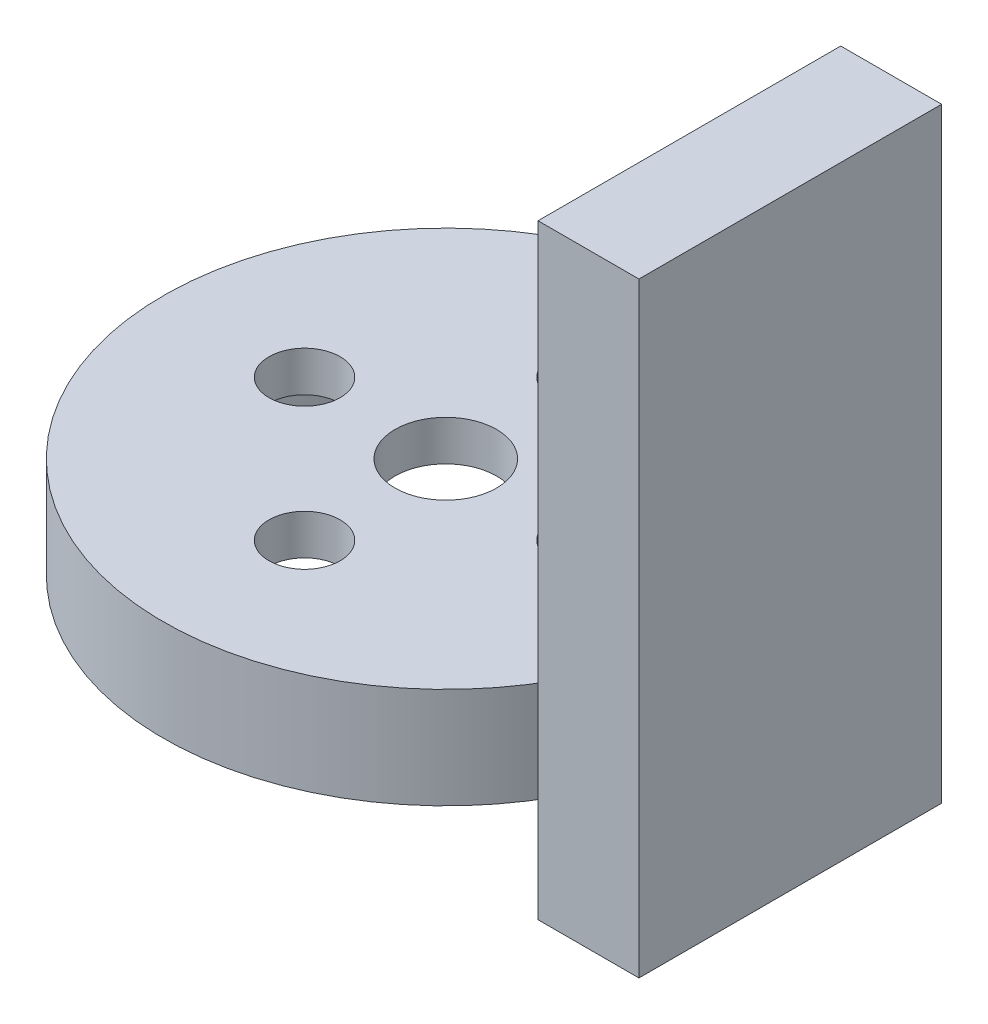
SolidWorks part; units mm, degrees
ref_plane "Front Plane" through (0, 0, 0) normal (0, 0, 1) x (1, 0, 0)
ref_plane "Top Plane" through (0, 0, 0) normal (0, 1, 0) x (1, 0, 0)
ref_plane "Right Plane" through (0, 0, 0) normal (1, 0, 0) x (0, 0, -1)
sketch "Sketch1" plane through (0, 0, 0) normal (0, 1, 0) x (1, 0, 0)
  circle A0 centre (0, 0) radius 14
  circle A1 centre (0, 0) radius 2.5173
  circle A2 centre (0, 7) radius 1.7621
  circle A3 centre (7, 0) radius 1.7621
  circle A4 centre (0, -7) radius 1.7621
  circle A5 centre (-7, 0) radius 1.7621
  point P15 (0, 0)
  dimension "D1" = 7
  dimension "D3" = 28
  dimension "D2" = 4
extrude "Boss-Extrude1" add sketch "Sketch1" along normal blind 5
sketch "Sketch4" plane through (0, 5, 0) normal (0, 1, 0) x (1, 0, 0)
  line L1 (22.0715, -2.5) -> (10.0715, -2.5)
  line L2 (22.0715, -2.5) -> (22.0715, 2.5)
  line L3 (22.0715, 2.5) -> (10.0715, 2.5)
  line L4 (10.0715, -2.5) -> (10.0715, 2.5)
  line L5 (22.0715, -2.5) -> (10.0715, 2.5) construction
  line L6 (22.0715, 2.5) -> (10.0715, -2.5) construction
  point P0 (16.0715, 0)
  dimension "D1" = 5
  dimension "D2" = 0
  dimension "D3" = 12
extrude "Boss-Extrude4" add sketch "Sketch4" against normal blind 5
sketch "Sketch6" plane through (0, 0, 0) normal (0, -1, 0) x (1, 0, 0)
  line L1 (22.0715, -2.5) -> (17.0715, -2.5)
  line L2 (22.0715, -2.5) -> (22.0715, 12.5)
  line L3 (22.0715, 12.5) -> (17.0715, 12.5)
  line L4 (17.0715, -2.5) -> (17.0715, 12.5)
  dimension "D1" = 5
  dimension "D2" = 15
extrude "Boss-Extrude5" add sketch "Sketch6" against normal blind 30
sketch "Sketch8" plane through (0, 0, 0) normal (0, -1, 0) x (1, 0, 0)
  circle A0 centre (0, 0) radius 10.75
extrude "Cut-Extrude2" cut sketch "Sketch8" against normal blind 3
fillet "Fillet1" radius 5 1 edges at (17.0715, 2.5, 2.5)
fillet "Fillet2" radius 1 2 edges at (13.775, 2.5, -2.5) (13.775, 2.5, 2.5)
